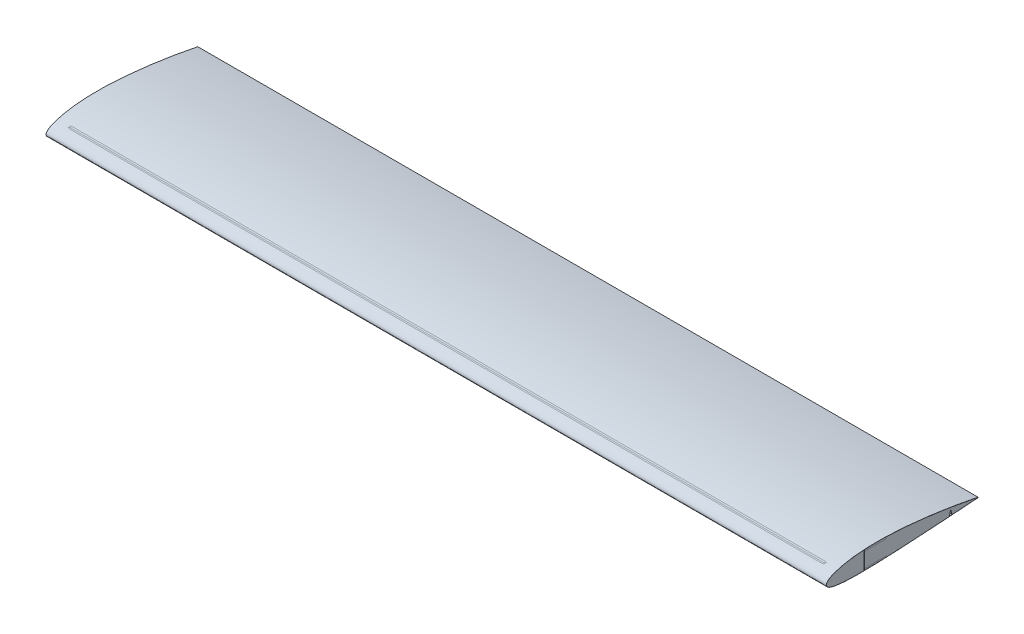
SolidWorks part; units mm, degrees
ref_plane "Front Plane" through (0, 0, 0) normal (0, 0, 1) x (1, 0, 0)
ref_plane "Top Plane" through (0, 0, 0) normal (0, 1, 0) x (1, 0, 0)
ref_plane "Right Plane" through (0, 0, 0) normal (1, 0, 0) x (0, 0, -1)
curve "Curve1"
  spline degree 3 poles (0, 25.4, 0.0064) (0, 25.2657, 0.0346) (0, 24.9974, 0.0911) (0, 24.5944, 0.1721) (0, 24.1917, 0.2509) (0, 23.7893, 0.3278) (0, 23.3874, 0.4029) (0, 22.9859, 0.4765) (0, 22.5851, 0.5485) (0, 22.1849, 0.619) (0, 21.7856, 0.688) (0, 21.3872, 0.7554) (0, 20.9898, 0.8212) (0, 20.5935, 0.8853) (0, 20.1985, 0.9476) (0, 19.8047, 1.0082) (0, 19.4123, 1.067) (0, 19.0215, 1.124) (0, 18.6322, 1.1792) (0, 18.2447, 1.2326) (0, 17.859, 1.2841) (0, 17.4751, 1.3339) (0, 17.0933, 1.382) (0, 16.7135, 1.4283) (0, 16.3359, 1.4729) (0, 15.9606, 1.5158) (0, 15.5877, 1.5571) (0, 15.2173, 1.5967) (0, 14.8494, 1.6346) (0, 14.4842, 1.6709) (0, 14.1217, 1.7054) (0, 13.7621, 1.7383) (0, 13.4054, 1.7695) (0, 13.0517, 1.7989) (0, 12.7011, 1.8265) (0, 12.3537, 1.8522) (0, 12.0097, 1.8761) (0, 11.6689, 1.8981) (0, 11.3317, 1.918) (0, 10.9979, 1.936) (0, 10.6678, 1.9519) (0, 10.3414, 1.9657) (0, 10.0188, 1.9774) (0, 9.7001, 1.9869) (0, 9.3853, 1.9942) (0, 9.0746, 1.9993) (0, 8.7679, 2.0022) (0, 8.4655, 2.0029) (0, 8.1673, 2.0014) (0, 7.8734, 1.9977) (0, 7.584, 1.9918) (0, 7.2991, 1.9837) (0, 7.0187, 1.9735) (0, 6.7429, 1.9612) (0, 6.4718, 1.9468) (0, 6.2055, 1.9304) (0, 5.944, 1.912) (0, 5.6874, 1.8917) (0, 5.4358, 1.8694) (0, 5.1892, 1.8454) (0, 4.9477, 1.8195) (0, 4.7114, 1.792) (0, 4.4802, 1.7628) (0, 4.2543, 1.7319) (0, 4.0338, 1.6995) (0, 3.8186, 1.6656) (0, 3.6089, 1.6303) (0, 3.4046, 1.5936) (0, 3.2059, 1.5556) (0, 3.0127, 1.5163) (0, 2.8252, 1.4759) (0, 2.6434, 1.4343) (0, 2.4673, 1.3917) (0, 2.297, 1.3481) (0, 2.1325, 1.3035) (0, 1.9738, 1.2581) (0, 1.8211, 1.2119) (0, 1.6742, 1.1649) (0, 1.5334, 1.1173) (0, 1.3985, 1.0691) (0, 1.2697, 1.0204) (0, 1.147, 0.9712) (0, 1.0304, 0.9215) (0, 0.9199, 0.8715) (0, 0.8155, 0.8212) (0, 0.7173, 0.7706) (0, 0.6254, 0.7198) (0, 0.5396, 0.6689) (0, 0.4601, 0.6178) (0, 0.3869, 0.5666) (0, 0.3199, 0.5153) (0, 0.2592, 0.4639) (0, 0.2049, 0.4126) (0, 0.1568, 0.3611) (0, 0.1151, 0.3097) (0, 0.0797, 0.2582) (0, 0.0507, 0.2067) (0, 0.0281, 0.1551) (0, 0.0119, 0.1034) (0, 0.0022, 0.0517) (0, -0.0011, 0.0014) (0, 0.0021, -0.0476) (0, 0.0119, -0.095) (0, 0.0281, -0.1421) (0, 0.0507, -0.1886) (0, 0.0797, -0.2345) (0, 0.1151, -0.2796) (0, 0.1568, -0.3238) (0, 0.2049, -0.3671) (0, 0.2593, -0.4092) (0, 0.32, -0.4502) (0, 0.387, -0.49) (0, 0.4602, -0.5285) (0, 0.5397, -0.5656) (0, 0.6255, -0.6013) (0, 0.7175, -0.6357) (0, 0.8157, -0.6686) (0, 0.92, -0.7001) (0, 1.0306, -0.7301) (0, 1.1472, -0.7588) (0, 1.2699, -0.786) (0, 1.3988, -0.8119) (0, 1.5336, -0.8364) (0, 1.6745, -0.8596) (0, 1.8213, -0.8815) (0, 1.974, -0.9021) (0, 2.1327, -0.9215) (0, 2.2972, -0.9397) (0, 2.4675, -0.9567) (0, 2.6436, -0.9725) (0, 2.8254, -0.9871) (0, 3.0129, -1.0006) (0, 3.206, -1.0129) (0, 3.4048, -1.0241) (0, 3.609, -1.0341) (0, 3.8188, -1.043) (0, 4.0339, -1.0507) (0, 4.2545, -1.0573) (0, 4.4804, -1.0628) (0, 4.7115, -1.0671) (0, 4.9478, -1.0703) (0, 5.1893, -1.0723) (0, 5.4359, -1.0732) (0, 5.6875, -1.073) (0, 5.9441, -1.0718) (0, 6.2056, -1.0694) (0, 6.4719, -1.0661) (0, 6.7429, -1.0617) (0, 7.0187, -1.0564) (0, 7.2991, -1.0502) (0, 7.584, -1.0431) (0, 7.8735, -1.0352) (0, 8.1673, -1.0265) (0, 8.4655, -1.017) (0, 8.7679, -1.0069) (0, 9.0746, -0.996) (0, 9.3853, -0.9846) (0, 9.7001, -0.9725) (0, 10.0188, -0.9599) (0, 10.3414, -0.9466) (0, 10.6678, -0.9328) (0, 10.9979, -0.9185) (0, 11.3316, -0.9035) (0, 11.6689, -0.888) (0, 12.0096, -0.8718) (0, 12.3537, -0.855) (0, 12.7011, -0.8375) (0, 13.0517, -0.8194) (0, 13.4053, -0.8005) (0, 13.762, -0.781) (0, 14.1217, -0.7608) (0, 14.4841, -0.7398) (0, 14.8494, -0.7181) (0, 15.2172, -0.6958) (0, 15.5877, -0.6729) (0, 15.9606, -0.6493) (0, 16.3359, -0.6253) (0, 16.7134, -0.6007) (0, 17.0932, -0.5758) (0, 17.475, -0.5506) (0, 17.8589, -0.5252) (0, 18.2446, -0.4996) (0, 18.6321, -0.4739) (0, 19.0214, -0.4481) (0, 19.4122, -0.4224) (0, 19.8046, -0.3966) (0, 20.1983, -0.3708) (0, 20.5934, -0.3449) (0, 20.9897, -0.3189) (0, 21.3871, -0.2926) (0, 21.7855, -0.2659) (0, 22.1848, -0.2386) (0, 22.585, -0.2108) (0, 22.9858, -0.1822) (0, 23.3872, -0.153) (0, 23.7892, -0.1231) (0, 24.1915, -0.0928) (0, 24.5941, -0.0626) (0, 24.997, -0.0331) (0, 25.2657, -0.0153) (0, 25.4, -0.0064) knots 0 0 0 0 0.007941 0.015868 0.023782 0.031684 0.039571 0.047444 0.055299 0.063136 0.070953 0.078747 0.086517 0.09426 0.101975 0.10966 0.117312 0.124931 0.132515 0.14006 0.147567 0.155033 0.162457 0.169836 0.17717 0.184456 0.191693 0.198879 0.206013 0.213092 0.220115 0.227081 0.233988 0.240834 0.247617 0.254336 0.260989 0.267575 0.274092 0.280538 0.286913 0.293214 0.299441 0.305592 0.311665 0.31766 0.323575 0.329409 0.33516 0.340829 0.346413 0.351912 0.357324 0.362648 0.367884 0.373031 0.378086 0.383051 0.387923 0.392702 0.397387 0.401977 0.406471 0.410868 0.415168 0.41937 0.423472 0.427475 0.431378 0.435179 0.438879 0.442477 0.445971 0.449362 0.45265 0.455833 0.458911 0.461884 0.464751 0.467513 0.470169 0.47272 0.475165 0.477504 0.479738 0.481867 0.483893 0.485816 0.487638 0.48936 0.490986 0.492517 0.493957 0.495311 0.496586 0.497786 0.498922 0.500002 0.50104 0.502047 0.503039 0.503952 0.504878 0.505831 0.506824 0.507866 0.508967 0.510136 0.51138 0.512704 0.514115 0.515615 0.517209 0.518901 0.520691 0.522584 0.524581 0.526682 0.528891 0.531207 0.533632 0.536166 0.538809 0.541562 0.544425 0.547398 0.550481 0.553673 0.556974 0.560384 0.563903 0.567529 0.571261 0.5751 0.579045 0.583094 0.587247 0.591503 0.595862 0.600321 0.60488 0.609539 0.614295 0.619148 0.624097 0.629141 0.634278 0.639507 0.644828 0.650237 0.655735 0.66132 0.666991 0.672745 0.678583 0.684501 0.690499 0.696575 0.702728 0.708956 0.715257 0.72163 0.728074 0.734587 0.741166 0.747811 0.75452 0.761292 0.768124 0.775014 0.781962 0.788966 0.796023 0.803132 0.810291 0.817498 0.824752 0.832051 0.839391 0.846773 0.854193 0.86165 0.869142 0.876666 0.884222 0.891806 0.899418 0.907055 0.914715 0.922398 0.9301 0.93782 0.945557 0.953308 0.961072 0.968847 0.97663 0.984418 0.99221 1 1 1 1
sketch "Sketch3" plane through (0, 0, 0) normal (1, 0, 0) x (0, 0, -1)
  line L1 (0, 12.7) -> (0, -12.7) construction
  line L2 (354.4824, 0.0886) -> (354.4824, -0.0886)
  line L3 (354.4824, 0) -> (0, 0) construction
  line L6 (290.9824, 0) -> (290.9824, 7.62) construction
  line L10 (290.9824, 7.62) -> (287.6544, -4.8003)
  line L11 (290.9824, 7.62) -> (294.1949, -4.3693)
  line L12 (287.6544, -4.8003) -> (290.9824, -6.35)
  line L13 (290.9824, -6.35) -> (294.1949, -4.3693)
  line L14 (290.9824, 0) -> (290.9824, -6.35) construction
  line L15 (88.9, 27.0678) -> (88.9, -14.9081) construction
  line L16 (88.9, 23.8928) -> (139.7, 23.8928)
  line L17 (139.7, 23.8928) -> (139.7, 27.5851)
  line L18 (88.9, 27.0678) -> (88.9, 23.8928)
  line L19 (355.092, 0.5833) -> (355.092, -0.6591)
  line L20 (88.9, -14.9081) -> (88.9, -11.7331)
  line L21 (88.9, -11.7331) -> (139.6922, -10.8456)
  line L22 (139.6922, -10.8456) -> (139.6922, -14.0206)
  line L23 (-0.6096, 17.8229) -> (-0.6096, -9.3347) construction
  spline S0 degree 1 poles (355.092, 0.5833) (355.092, -0.6591) knots 0 0 1 1 construction
  spline S1 degree 3 poles (354.4824, 0.0886) (352.6082, 0.483) (348.863, 1.271) (343.2392, 2.4007) (337.6192, 3.5012) (332.0035, 4.5734) (326.3937, 5.6217) (320.791, 6.6479) (313.3412, 7.9862) (302.2175, 9.9271) (289.2822, 12.0693) (276.4183, 14.0744) (265.4902, 15.6897) (251.1156, 17.6976) (236.874, 19.5167) (222.7822, 21.1545) (212.4103, 22.2822) (202.1815, 23.3173) (192.1062, 24.2587) (182.1944, 25.104) (172.456, 25.8491) (161.3668, 26.5921) (149.0219, 27.2602) (135.5235, 27.7529) (122.5206, 27.9717) (110.0426, 27.9126) (99.359, 27.6139) (90.383, 27.1766) (83.0183, 26.6917) (75.9268, 26.0988) (69.1158, 25.4036) (62.5921, 24.6121) (56.3622, 23.7307) (50.4324, 22.7661) (44.8087, 21.725) (39.4966, 20.6143) (35.2734, 19.6224) (31.3121, 18.6077) (28.3048, 17.7721) (25.414, 16.8975) (23.365, 16.2423) (21.3993, 15.5778) (19.5174, 14.9049) (17.7198, 14.2245) (16.0069, 13.5374) (14.3791, 12.8445) (12.8369, 12.1465) (11.3806, 11.4442) (10.0105, 10.7383) (8.727, 10.0294) (7.5304, 9.318) (6.4209, 8.6048) (5.3988, 7.8902) (4.4643, 7.1745) (3.6176, 6.458) (2.8589, 5.7409) (2.1883, 5.0233) (1.6061, 4.3053) (1.1124, 3.5867) (0.7076, 2.8675) (0.392, 2.1475) (0.166, 1.4266) (0.0306, 0.7051) (-0.0151, 0.0023) (0.03, -0.6811) (0.1662, -1.3427) (0.3921, -1.9994) (0.7078, -2.649) (1.1127, -3.2894) (1.6065, -3.919) (2.189, -4.5362) (2.8598, -5.1397) (3.6189, -5.728) (4.4659, -6.3001) (5.4008, -6.855) (6.4232, -7.3918) (7.533, -7.9099) (8.7299, -8.4087) (10.0137, -8.8878) (11.384, -9.3471) (12.8406, -9.7864) (14.383, -10.2059) (16.0109, -10.6056) (17.724, -10.9858) (19.5217, -11.3467) (21.4037, -11.6888) (23.3694, -12.0125) (25.4185, -12.318) (27.5503, -12.6058) (29.7644, -12.8763) (32.0603, -13.1297) (35.2816, -13.4506) (39.509, -13.8076) (44.8204, -14.1653) (50.4434, -14.4593) (56.3724, -14.6897) (62.6015, -14.8564) (69.1244, -14.9593) (75.9346, -14.999) (83.0252, -14.9771) (90.3891, -14.8962) (98.0187, -14.7598) (105.9066, -14.5724) (114.0447, -14.339) (122.4249, -14.0642) (131.0387, -13.7525) (139.8776, -13.407) (148.9326, -13.0293) (161.4123, -12.4772) (174.1486, -11.8638) (187.1282, -11.1819) (197.1228, -10.6261) (207.2759, -10.0307) (219.334, -9.2899) (231.5492, -8.5038) (243.9097, -7.6885) (254.647, -6.9749) (263.6596, -6.3774) (272.7492, -5.778) (281.9067, -5.1773) (292.9484, -4.4535) (302.1903, -3.8388) (309.6118, -3.3326) (315.196, -2.9438) (320.79, -2.5451) (326.3924, -2.1363) (332.0019, -1.7188) (337.6169, -1.2958) (343.236, -0.8748) (348.8576, -0.4618) (352.6075, -0.213) (354.4824, -0.0886) knots 0 0 0 0 0.007941 0.015868 0.023782 0.031684 0.039571 0.047444 0.055299 0.070953 0.09426 0.10966 0.124931 0.14006 0.169836 0.184456 0.198879 0.213092 0.227081 0.240834 0.254336 0.267575 0.286913 0.305592 0.323575 0.340829 0.357324 0.367884 0.378086 0.387923 0.397387 0.406471 0.415168 0.423472 0.431378 0.438879 0.445971 0.449362 0.455833 0.458911 0.461884 0.464751 0.467513 0.470169 0.47272 0.475165 0.477504 0.479738 0.481867 0.483893 0.485816 0.487638 0.48936 0.490986 0.492517 0.493957 0.495311 0.496586 0.497786 0.498922 0.500002 0.50104 0.502047 0.503039 0.503952 0.504878 0.505831 0.506824 0.507866 0.508967 0.510136 0.51138 0.512704 0.514115 0.515615 0.517209 0.518901 0.520691 0.522584 0.524581 0.526682 0.528891 0.531207 0.533632 0.536166 0.538809 0.541562 0.544425 0.547398 0.550481 0.553673 0.556974 0.563903 0.571261 0.579045 0.587247 0.595862 0.60488 0.614295 0.624097 0.634278 0.644828 0.655735 0.666991 0.678583 0.690499 0.702728 0.715257 0.728074 0.75452 0.768124 0.781962 0.796023 0.810291 0.832051 0.846773 0.86165 0.876666 0.884222 0.899418 0.914715 0.9301 0.93782 0.945557 0.953308 0.961072 0.968847 0.97663 0.984418 0.99221 1 1 1 1
  spline S2 degree 3 poles (355.092, 0.5833) (340.3127, 3.693) (310.6199, 9.2752) (265.8868, 16.4895) (228.4235, 21.2496) (198.3754, 24.3469) (175.8005, 26.2799) (153.1859, 27.7344) (130.5343, 28.5669) (111.6397, 28.5951) (96.5306, 28.1208) (85.2091, 27.4901) (73.9067, 26.5545) (62.6352, 25.2772) (51.4111, 23.6096) (42.1176, 21.8373) (34.7401, 20.1344) (29.2444, 18.6936) (23.7983, 17.061) (18.4203, 15.1959) (13.1437, 13.0326) (8.8802, 10.8891) (5.6308, 8.8467) (3.3237, 7.0865) (1.2453, 5.0033) (-0.1004, 2.8369) (-0.5231, 1.1906) (-0.6134, 0.2722) (-0.6145, -0.2638) (-0.5195, -1.1773) (-0.1862, -2.322) (0.8469, -4.1077) (2.6493, -5.87) (5.1185, -7.4554) (7.7371, -8.698) (11.3328, -10.0346) (15.9372, -11.2769) (21.5293, -12.3685) (27.1547, -13.1959) (32.7972, -13.8378) (40.3339, -14.5078) (49.7691, -15.075) (61.0997, -15.4585) (72.4323, -15.615) (83.7634, -15.5946) (95.0915, -15.437) (109.9642, -15.0928) (122.9439, -14.664) (135.9206, -14.1746) (143.6903, -13.8607) (157.1163, -13.285) (174.3107, -12.4807) (196.9278, -11.2693) (227.0713, -9.4426) (257.1966, -7.4054) (287.3245, -5.4343) (309.9221, -3.947) (332.5149, -2.3034) (347.562, -1.1587) (355.092, -0.6591) knots -0.000684 -0.000684 -0.000684 -0.000684 0.061908 0.1245 0.187092 0.218388 0.249684 0.28098 0.312276 0.343572 0.35922 0.374868 0.390516 0.406164 0.421812 0.43746 0.445284 0.453108 0.460932 0.468756 0.47658 0.484404 0.488316 0.492228 0.49614 0.500052 0.502008 0.502527 0.503505 0.503994 0.50592 0.507876 0.511788 0.5157 0.519612 0.523524 0.531348 0.539172 0.546996 0.55482 0.562644 0.578292 0.59394 0.609588 0.625236 0.640884 0.656532 0.68689 0.694714 0.710362 0.719124 0.75042 0.781716 0.813012 0.875604 0.9069 0.938196 0.969492 1.000788 1.000788 1.000788 1.000788
  point P7 (0, 0)
  point P9 (290.9824, 0)
  dimension "D1" = 354.4824
  dimension "D2" = 63.5
  dimension "D3" = 15
  dimension "D4" = 15
  dimension "D5" = 7.62
  dimension "D6" = 6.35
  dimension "D7" = 88.9
  dimension "D8" = 50.8
  dimension "D9" = 3.175
  dimension "D11" = 3.175
  dimension "D10" = 0.6096
extrude "Boss-Extrude1" add sketch "Sketch3" along normal mid plane 1828.8 contours S1 L2
sketch "Sketch4" plane through (914.4, 0, 0) normal (1, 0, 0) x (0, 0, -1)
  line L0 (88.9, -14.9081) -> (88.9, -11.7331) construction
  line L1 (88.9, -11.7331) -> (139.6922, -10.8456) construction
  line L2 (139.6922, -10.8456) -> (139.6922, -14.0206) construction
  line L3 (139.7, 23.8928) -> (139.7, 27.5851) construction
  line L4 (88.9, 27.0678) -> (88.9, 23.8928) construction
  line L5 (88.9, 23.8928) -> (139.7, 23.8928) construction
  line L6 (88.9, -14.9081) -> (88.9, -11.7331)
  line L7 (88.9, -11.7331) -> (139.6922, -10.8456)
  line L8 (139.6922, -10.8456) -> (139.6922, -14.0206)
  line L9 (139.7, 23.8928) -> (139.7, 27.5851)
  line L10 (88.9, 27.0678) -> (88.9, 23.8928)
  line L11 (88.9, 23.8928) -> (139.7, 23.8928)
split "Split1" trim tools "Sketch4" bodies to split 101 resulting bodies 103 104 105
sketch "Sketch5" plane through (914.4, 0, 0) normal (1, 0, 0) x (0, 0, -1)
  line L1 (88.9, 27.0678) -> (88.2904, 27.0678)
  line L2 (88.9, 27.0678) -> (88.9, -14.9081)
  line L3 (88.9, -14.9081) -> (88.2904, -14.9081)
  line L4 (88.2904, 27.0678) -> (88.2904, -14.9081)
  dimension "D1" = 0.6096
extrude "Cut-Extrude2" cut sketch "Sketch5" against normal through all and the other way through all
sketch "Sketch6" plane through (0, 0, 0) normal (1, 0, 0) x (0, 0, -1)
  line L0 (355.092, 0.5833) -> (355.092, -0.6591) construction
  line L1 (354.4824, 0.0886) -> (354.4824, -0.0886) construction
  line L2 (355.092, 0.5833) -> (355.092, -0.6591)
  line L3 (354.4824, 0.0886) -> (354.4824, -0.0886)
  spline S0 degree 3 poles (865.9869, -859.0536) (796.8228, -130.8715) (543.8388, -28.3369) (265.8868, 16.4895) (228.4235, 21.2496) (198.3754, 24.3469) (175.8005, 26.2799) (153.1859, 27.7344) (130.5343, 28.5669) (111.6397, 28.5951) (96.5306, 28.1208) (85.2091, 27.4901) (73.9067, 26.5545) (62.6352, 25.2772) (51.4111, 23.6096) (42.1176, 21.8373) (34.7401, 20.1344) (29.2444, 18.6936) (23.7983, 17.061) (18.4203, 15.1959) (13.1437, 13.0326) (8.8802, 10.8891) (5.6308, 8.8467) (3.3237, 7.0865) (1.2453, 5.0033) (-0.1004, 2.8369) (-0.5231, 1.1906) (-0.6134, 0.2722) (-0.6145, -0.2638) (-0.5195, -1.1773) (-0.1862, -2.322) (0.8469, -4.1077) (2.6493, -5.87) (5.1185, -7.4554) (7.7371, -8.698) (11.3328, -10.0346) (15.9372, -11.2769) (21.5293, -12.3685) (27.1547, -13.1959) (32.7972, -13.8378) (40.3339, -14.5078) (49.7691, -15.075) (61.0997, -15.4585) (72.4323, -15.615) (83.7634, -15.5946) (95.0915, -15.437) (109.9642, -15.0928) (122.9439, -14.664) (135.9206, -14.1746) (143.6903, -13.8607) (157.1163, -13.285) (174.3107, -12.4807) (196.9278, -11.2693) (227.0713, -9.4426) (257.1966, -7.4054) (287.3245, -5.4343) (309.9221, -3.947) (488.7981, 9.0665) (658.2328, 27.8647) (923.0256, -823.6825) knots -0.979666 -0.979666 -0.979666 -0.979666 0.061908 0.1245 0.187092 0.218388 0.249684 0.28098 0.312276 0.343572 0.35922 0.374868 0.390516 0.406164 0.421812 0.43746 0.445284 0.453108 0.460932 0.468756 0.47658 0.484404 0.488316 0.492228 0.49614 0.500052 0.502008 0.502527 0.503505 0.503994 0.50592 0.507876 0.511788 0.5157 0.519612 0.523524 0.531348 0.539172 0.546996 0.55482 0.562644 0.578292 0.59394 0.609588 0.625236 0.640884 0.656532 0.68689 0.694714 0.710362 0.719124 0.75042 0.781716 0.813012 0.875604 0.9069 0.938196 0.969492 1.650249 1.650249 1.650249 1.650249 only from (355.092, 0.5833) to (355.092, -0.6591) construction
  spline S1 degree 3 poles (818.2972, 885.9951) (528.0596, -56.9696) (438.7893, -16.7935) (343.2392, 2.4007) (337.6192, 3.5012) (332.0035, 4.5734) (326.3937, 5.6217) (320.791, 6.6479) (313.3412, 7.9862) (302.2175, 9.9271) (289.2822, 12.0693) (276.4183, 14.0744) (265.4902, 15.6897) (251.1156, 17.6976) (236.874, 19.5167) (222.7822, 21.1545) (212.4103, 22.2822) (202.1815, 23.3173) (192.1062, 24.2587) (182.1944, 25.104) (172.456, 25.8491) (161.3668, 26.5921) (149.0219, 27.2602) (135.5235, 27.7529) (122.5206, 27.9717) (110.0426, 27.9126) (99.359, 27.6139) (90.383, 27.1766) (83.0183, 26.6917) (75.9268, 26.0988) (69.1158, 25.4036) (62.5921, 24.6121) (56.3622, 23.7307) (50.4324, 22.7661) (44.8087, 21.725) (39.4966, 20.6143) (35.2734, 19.6224) (31.3121, 18.6077) (28.3048, 17.7721) (25.414, 16.8975) (23.365, 16.2423) (21.3993, 15.5778) (19.5174, 14.9049) (17.7198, 14.2245) (16.0069, 13.5374) (14.3791, 12.8445) (12.8369, 12.1465) (11.3806, 11.4442) (10.0105, 10.7383) (8.727, 10.0294) (7.5304, 9.318) (6.4209, 8.6048) (5.3988, 7.8902) (4.4643, 7.1745) (3.6176, 6.458) (2.8589, 5.7409) (2.1883, 5.0233) (1.6061, 4.3053) (1.1124, 3.5867) (0.7076, 2.8675) (0.392, 2.1475) (0.166, 1.4266) (0.0306, 0.7051) (-0.0151, 0.0023) (0.03, -0.6811) (0.1662, -1.3427) (0.3921, -1.9994) (0.7078, -2.649) (1.1127, -3.2894) (1.6065, -3.919) (2.189, -4.5362) (2.8598, -5.1397) (3.6189, -5.728) (4.4659, -6.3001) (5.4008, -6.855) (6.4232, -7.3918) (7.533, -7.9099) (8.7299, -8.4087) (10.0137, -8.8878) (11.384, -9.3471) (12.8406, -9.7864) (14.383, -10.2059) (16.0109, -10.6056) (17.724, -10.9858) (19.5217, -11.3467) (21.4037, -11.6888) (23.3694, -12.0125) (25.4185, -12.318) (27.5503, -12.6058) (29.7644, -12.8763) (32.0603, -13.1297) (35.2816, -13.4506) (39.509, -13.8076) (44.8204, -14.1653) (50.4434, -14.4593) (56.3724, -14.6897) (62.6015, -14.8564) (69.1244, -14.9593) (75.9346, -14.999) (83.0252, -14.9771) (90.3891, -14.8962) (98.0187, -14.7598) (105.9066, -14.5724) (114.0447, -14.339) (122.4249, -14.0642) (131.0387, -13.7525) (139.8776, -13.407) (148.9326, -13.0293) (161.4123, -12.4772) (174.1486, -11.8638) (187.1282, -11.1819) (197.1228, -10.6261) (207.2759, -10.0307) (219.334, -9.2899) (231.5492, -8.5038) (243.9097, -7.6885) (254.647, -6.9749) (263.6596, -6.3774) (272.7492, -5.778) (281.9067, -5.1773) (292.9484, -4.4535) (302.1903, -3.8388) (309.6118, -3.3326) (315.196, -2.9438) (320.79, -2.5451) (326.3924, -2.1363) (332.0019, -1.7188) (337.6169, -1.2958) (343.236, -0.8748) (446.9347, 6.7445) (550.1272, -5.4226) (582.4739, 973.4848) knots -0.380285 -0.380285 -0.380285 -0.380285 0.007941 0.015868 0.023782 0.031684 0.039571 0.047444 0.055299 0.070953 0.09426 0.10966 0.124931 0.14006 0.169836 0.184456 0.198879 0.213092 0.227081 0.240834 0.254336 0.267575 0.286913 0.305592 0.323575 0.340829 0.357324 0.367884 0.378086 0.387923 0.397387 0.406471 0.415168 0.423472 0.431378 0.438879 0.445971 0.449362 0.455833 0.458911 0.461884 0.464751 0.467513 0.470169 0.47272 0.475165 0.477504 0.479738 0.481867 0.483893 0.485816 0.487638 0.48936 0.490986 0.492517 0.493957 0.495311 0.496586 0.497786 0.498922 0.500002 0.50104 0.502047 0.503039 0.503952 0.504878 0.505831 0.506824 0.507866 0.508967 0.510136 0.51138 0.512704 0.514115 0.515615 0.517209 0.518901 0.520691 0.522584 0.524581 0.526682 0.528891 0.531207 0.533632 0.536166 0.538809 0.541562 0.544425 0.547398 0.550481 0.553673 0.556974 0.563903 0.571261 0.579045 0.587247 0.595862 0.60488 0.614295 0.624097 0.634278 0.644828 0.655735 0.666991 0.678583 0.690499 0.702728 0.715257 0.728074 0.75452 0.768124 0.781962 0.796023 0.810291 0.832051 0.846773 0.86165 0.876666 0.884222 0.899418 0.914715 0.9301 0.93782 0.945557 0.953308 0.961072 0.968847 0.97663 0.984418 0.99221 1.407729 1.407729 1.407729 1.407729 only from (354.4824, 0.0886) to (354.4824, -0.0886) construction
  spline S2 degree 3 poles (355.092, 0.5833) (340.3127, 3.693) (310.6199, 9.2752) (265.8868, 16.4895) (228.4235, 21.2496) (198.3754, 24.3469) (175.8005, 26.2799) (153.1859, 27.7344) (130.5343, 28.5669) (111.6397, 28.5951) (96.5306, 28.1208) (85.2091, 27.4901) (73.9067, 26.5545) (62.6352, 25.2772) (51.4111, 23.6096) (42.1176, 21.8373) (34.7401, 20.1344) (29.2444, 18.6936) (23.7983, 17.061) (18.4203, 15.1959) (13.1437, 13.0326) (8.8802, 10.8891) (5.6308, 8.8467) (3.3237, 7.0865) (1.2453, 5.0033) (-0.1004, 2.8369) (-0.5231, 1.1906) (-0.6134, 0.2722) (-0.6145, -0.2638) (-0.5195, -1.1773) (-0.1862, -2.322) (0.8469, -4.1077) (2.6493, -5.87) (5.1185, -7.4554) (7.7371, -8.698) (11.3328, -10.0346) (15.9372, -11.2769) (21.5293, -12.3685) (27.1547, -13.1959) (32.7972, -13.8378) (40.3339, -14.5078) (49.7691, -15.075) (61.0997, -15.4585) (72.4323, -15.615) (83.7634, -15.5946) (95.0915, -15.437) (109.9642, -15.0928) (122.9439, -14.664) (135.9206, -14.1746) (143.6903, -13.8607) (157.1163, -13.285) (174.3107, -12.4807) (196.9278, -11.2693) (227.0713, -9.4426) (257.1966, -7.4054) (287.3245, -5.4343) (309.9221, -3.947) (332.5149, -2.3034) (347.562, -1.1587) (355.092, -0.6591) knots -0.000684 -0.000684 -0.000684 -0.000684 0.061908 0.1245 0.187092 0.218388 0.249684 0.28098 0.312276 0.343572 0.35922 0.374868 0.390516 0.406164 0.421812 0.43746 0.445284 0.453108 0.460932 0.468756 0.47658 0.484404 0.488316 0.492228 0.49614 0.500052 0.502008 0.502527 0.503505 0.503994 0.50592 0.507876 0.511788 0.5157 0.519612 0.523524 0.531348 0.539172 0.546996 0.55482 0.562644 0.578292 0.59394 0.609588 0.625236 0.640884 0.656532 0.68689 0.694714 0.710362 0.719124 0.75042 0.781716 0.813012 0.875604 0.9069 0.938196 0.969492 1.000788 1.000788 1.000788 1.000788
  spline S3 degree 3 poles (354.4824, 0.0886) (352.6082, 0.483) (348.863, 1.271) (343.2392, 2.4007) (337.6192, 3.5012) (332.0035, 4.5734) (326.3937, 5.6217) (320.791, 6.6479) (313.3412, 7.9862) (302.2175, 9.9271) (289.2822, 12.0693) (276.4183, 14.0744) (265.4902, 15.6897) (251.1156, 17.6976) (236.874, 19.5167) (222.7822, 21.1545) (212.4103, 22.2822) (202.1815, 23.3173) (192.1062, 24.2587) (182.1944, 25.104) (172.456, 25.8491) (161.3668, 26.5921) (149.0219, 27.2602) (135.5235, 27.7529) (122.5206, 27.9717) (110.0426, 27.9126) (99.359, 27.6139) (90.383, 27.1766) (83.0183, 26.6917) (75.9268, 26.0988) (69.1158, 25.4036) (62.5921, 24.6121) (56.3622, 23.7307) (50.4324, 22.7661) (44.8087, 21.725) (39.4966, 20.6143) (35.2734, 19.6224) (31.3121, 18.6077) (28.3048, 17.7721) (25.414, 16.8975) (23.365, 16.2423) (21.3993, 15.5778) (19.5174, 14.9049) (17.7198, 14.2245) (16.0069, 13.5374) (14.3791, 12.8445) (12.8369, 12.1465) (11.3806, 11.4442) (10.0105, 10.7383) (8.727, 10.0294) (7.5304, 9.318) (6.4209, 8.6048) (5.3988, 7.8902) (4.4643, 7.1745) (3.6176, 6.458) (2.8589, 5.7409) (2.1883, 5.0233) (1.6061, 4.3053) (1.1124, 3.5867) (0.7076, 2.8675) (0.392, 2.1475) (0.166, 1.4266) (0.0306, 0.7051) (-0.0151, 0.0023) (0.03, -0.6811) (0.1662, -1.3427) (0.3921, -1.9994) (0.7078, -2.649) (1.1127, -3.2894) (1.6065, -3.919) (2.189, -4.5362) (2.8598, -5.1397) (3.6189, -5.728) (4.4659, -6.3001) (5.4008, -6.855) (6.4232, -7.3918) (7.533, -7.9099) (8.7299, -8.4087) (10.0137, -8.8878) (11.384, -9.3471) (12.8406, -9.7864) (14.383, -10.2059) (16.0109, -10.6056) (17.724, -10.9858) (19.5217, -11.3467) (21.4037, -11.6888) (23.3694, -12.0125) (25.4185, -12.318) (27.5503, -12.6058) (29.7644, -12.8763) (32.0603, -13.1297) (35.2816, -13.4506) (39.509, -13.8076) (44.8204, -14.1653) (50.4434, -14.4593) (56.3724, -14.6897) (62.6015, -14.8564) (69.1244, -14.9593) (75.9346, -14.999) (83.0252, -14.9771) (90.3891, -14.8962) (98.0187, -14.7598) (105.9066, -14.5724) (114.0447, -14.339) (122.4249, -14.0642) (131.0387, -13.7525) (139.8776, -13.407) (148.9326, -13.0293) (161.4123, -12.4772) (174.1486, -11.8638) (187.1282, -11.1819) (197.1228, -10.6261) (207.2759, -10.0307) (219.334, -9.2899) (231.5492, -8.5038) (243.9097, -7.6885) (254.647, -6.9749) (263.6596, -6.3774) (272.7492, -5.778) (281.9067, -5.1773) (292.9484, -4.4535) (302.1903, -3.8388) (309.6118, -3.3326) (315.196, -2.9438) (320.79, -2.5451) (326.3924, -2.1363) (332.0019, -1.7188) (337.6169, -1.2958) (343.236, -0.8748) (348.8576, -0.4618) (352.6075, -0.213) (354.4824, -0.0886) knots 0 0 0 0 0.007941 0.015868 0.023782 0.031684 0.039571 0.047444 0.055299 0.070953 0.09426 0.10966 0.124931 0.14006 0.169836 0.184456 0.198879 0.213092 0.227081 0.240834 0.254336 0.267575 0.286913 0.305592 0.323575 0.340829 0.357324 0.367884 0.378086 0.387923 0.397387 0.406471 0.415168 0.423472 0.431378 0.438879 0.445971 0.449362 0.455833 0.458911 0.461884 0.464751 0.467513 0.470169 0.47272 0.475165 0.477504 0.479738 0.481867 0.483893 0.485816 0.487638 0.48936 0.490986 0.492517 0.493957 0.495311 0.496586 0.497786 0.498922 0.500002 0.50104 0.502047 0.503039 0.503952 0.504878 0.505831 0.506824 0.507866 0.508967 0.510136 0.51138 0.512704 0.514115 0.515615 0.517209 0.518901 0.520691 0.522584 0.524581 0.526682 0.528891 0.531207 0.533632 0.536166 0.538809 0.541562 0.544425 0.547398 0.550481 0.553673 0.556974 0.563903 0.571261 0.579045 0.587247 0.595862 0.60488 0.614295 0.624097 0.634278 0.644828 0.655735 0.666991 0.678583 0.690499 0.702728 0.715257 0.728074 0.75452 0.768124 0.781962 0.796023 0.810291 0.832051 0.846773 0.86165 0.876666 0.884222 0.899418 0.914715 0.9301 0.93782 0.945557 0.953308 0.961072 0.968847 0.97663 0.984418 0.99221 1 1 1 1
extrude "Boss-Extrude3" add sketch "Sketch3<4>" along normal mid plane 1828.8 separate body contours S1 L2 | S2 L19
sketch "Sketch3<4>" plane through (0, 0, 0) normal (1, 0, 0) x (0, 0, -1) same geometry as "Sketch3"
extrude "Cut-Extrude1" cut sketch "Sketch3<3>" against normal through all both and the other way through all contours L12 L13 L11 L10
sketch "Sketch3<3>" plane through (0, 0, 0) normal (1, 0, 0) x (0, 0, -1) same geometry as "Sketch3"
sketch "Sketch7" plane through (0, 0, 0) normal (0, 1, 0) x (1, 0, 0)
  line L0 (914.4, 88.2904) -> (-914.4, 88.2904) construction
  line L1 (0, -0.6096) -> (0, 355.092) construction
  line L2 (279.4, 139.6922) -> (368.3, 139.6922)
  line L3 (279.4, 139.6922) -> (279.4, 190.4922)
  line L4 (279.4, 190.4922) -> (368.3, 190.4922)
  line L5 (368.3, 139.6922) -> (368.3, 190.4922)
  line L6 (914.4, 88.9) -> (914.4, 139.7) construction
  line L7 (590.4, 139.6922) -> (660.4, 139.6922)
  line L8 (590.4, 139.6922) -> (590.4, 199.6922)
  line L9 (590.4, 199.6922) -> (660.4, 199.6922)
  line L10 (660.4, 139.6922) -> (660.4, 199.6922)
  line L11 (914.4, 139.6922) -> (-914.4, 139.6922) construction
  line L12 (158.75, 139.6922) -> (158.75, 199.6922)
  line L13 (158.75, 199.6922) -> (228.75, 199.6922)
  line L14 (228.75, 139.6922) -> (228.75, 199.6922)
  line L15 (158.75, 139.6922) -> (228.75, 139.6922)
  line L16 (0, -24.3155) -> (0, 24.3155) construction
  line L17 (-158.75, 139.6922) -> (-158.75, 199.6922)
  line L18 (-158.75, 199.6922) -> (-228.75, 199.6922)
  line L19 (-368.3, 139.6922) -> (-368.3, 190.4922)
  line L20 (-228.75, 139.6922) -> (-228.75, 199.6922)
  line L21 (-158.75, 139.6922) -> (-228.75, 139.6922)
  line L22 (-279.4, 190.4922) -> (-368.3, 190.4922)
  line L23 (-279.4, 139.6922) -> (-279.4, 190.4922)
  line L24 (-279.4, 139.6922) -> (-368.3, 139.6922)
  line L25 (-590.4, 139.6922) -> (-660.4, 139.6922)
  line L26 (-660.4, 139.6922) -> (-660.4, 199.6922)
  line L27 (-590.4, 199.6922) -> (-660.4, 199.6922)
  line L28 (-590.4, 139.6922) -> (-590.4, 199.6922)
  dimension "D1" = 279.4
  dimension "D2" = 88.9
  dimension "D3" = 50.8
  dimension "D4" = 254
  dimension "D5" = 70
  dimension "D6" = 60
  dimension "D8" = 158.75
  dimension "D7" = 2
extrude "Cut-Extrude3" cut sketch "Sketch7" along normal blind 30 from offset 15.24 offset against normal yes
ref_plane "Leading Edge - with skin" through (0, 0, 0.6096) normal (0, 0, 1) x (1, 0, 0)
